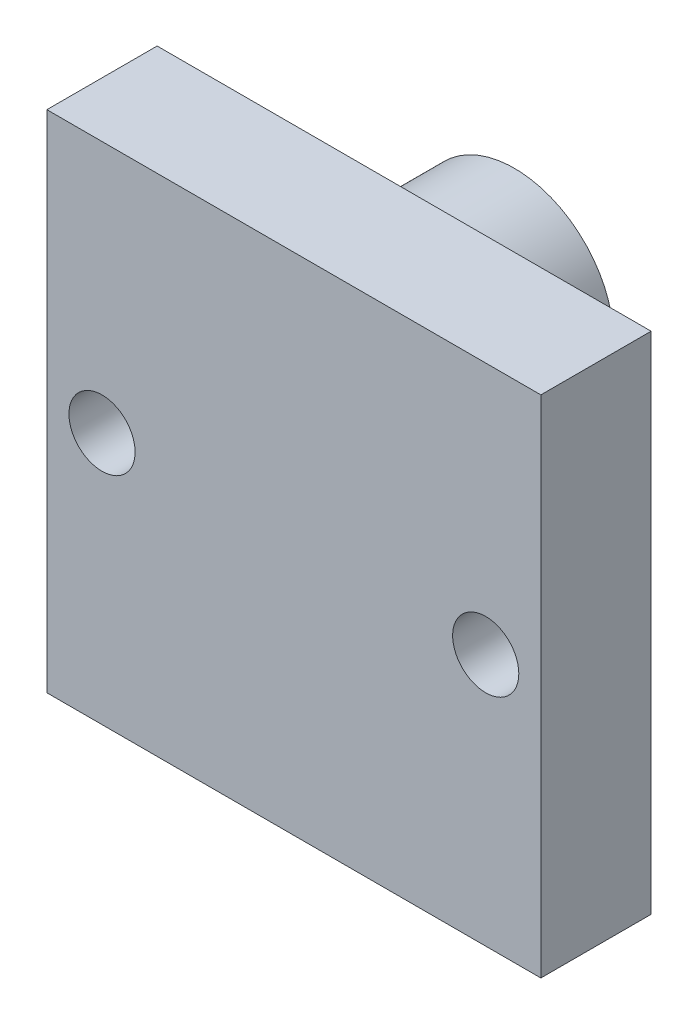
SolidWorks part; units mm, degrees
ref_plane "Front Plane" through (0, 0, 0) normal (0, 0, 1) x (1, 0, 0)
ref_plane "Top Plane" through (0, 0, 0) normal (0, 1, 0) x (1, 0, 0)
ref_plane "Right Plane" through (0, 0, 0) normal (1, 0, 0) x (0, 0, -1)
sketch "Sketch1" plane through (0, 0, 0) normal (0, 0, 1) x (1, 0, 0)
  line L1 (-11.2, 11.45) -> (11.2, 11.45)
  line L2 (-11.2, 11.45) -> (-11.2, -11.45)
  line L3 (-11.2, -11.45) -> (11.2, -11.45)
  line L4 (11.2, 11.45) -> (11.2, -11.45)
  line L5 (-11.2, 11.45) -> (11.2, -11.45) construction
  line L6 (-11.2, -11.45) -> (11.2, 11.45) construction
  point P0 (0, 0)
  dimension "D1" = 22.4
  dimension "D2" = 22.9
extrude "Boss-Extrude1" add sketch "Sketch1" along normal blind 5
sketch "Sketch2" plane through (0, 0, 5) normal (0, 0, 1) x (1, 0, 0)
  line L0 (0, 0) -> (-11.2, 0) construction
  line L1 (-11.2, 11.45) -> (-11.2, -11.45) construction
  line L2 (0, 0) -> (11.2, 0) construction
  line L3 (11.2, -11.45) -> (11.2, 11.45) construction
  line L4 (-11.2, 11.45) -> (-8.7, 11.45) construction
  line L5 (11.2, 11.45) -> (-11.2, 11.45) construction
  line L6 (11.2, 11.45) -> (8.7, 11.45) construction
  line L7 (-8.7, 11.45) -> (-8.7, 0) construction
  line L8 (8.7, 11.45) -> (8.7, 0) construction
  circle A0 centre (-8.7, 0) radius 1.5
  circle A1 centre (8.7, 0) radius 1.5
  dimension "D1" = 2.5
  dimension "D2" = 2.5
extrude "Cut-Extrude1" cut sketch "Sketch2" against normal blind 5
sketch "Sketch4" plane through (0, 0, 0) normal (0, 0, -1) x (-1, 0, 0)
  line L0 (-11.2, 11.45) -> (11.2, 11.45) construction
  line L1 (-11.2, 11.45) -> (11.2, 11.45) construction
  line L2 (0, 11.45) -> (0, 5.25) construction
  circle A0 centre (0, 5.25) radius 4.5
  dimension "D1" = 6.2
extrude "Boss-Extrude3" add sketch "Sketch4" along normal blind 5 contours A0
